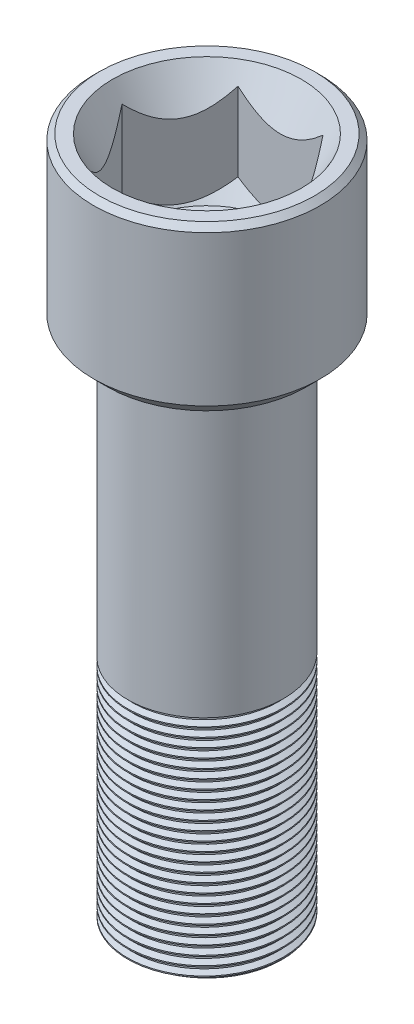
SolidWorks part; units mm, degrees
ref_plane "Front Plane" through (0, 0, 0) normal (0, 0, 1) x (1, 0, 0)
ref_plane "Top Plane" through (0, 0, 0) normal (0, 1, 0) x (1, 0, 0)
ref_plane "Right Plane" through (0, 0, 0) normal (1, 0, 0) x (0, 0, -1)
sketch "Sketch1" plane through (0, 0, 0) normal (0, 1, 0) x (1, 0, 0)
  circle A0 centre (0, 0) radius 4
  dimension "D1" = 8
extrude "Boss-Extrude1" add sketch "Sketch1" against normal blind 12
sketch "Sketch2" plane through (0, -12, 0) normal (0, -1, 0) x (1, 0, 0)
  circle A0 centre (0, 0) radius 2.75
  dimension "D1" = 5.5
extrude "Boss-Extrude2" add sketch "Sketch2" along normal blind 20
sketch "Sketch3" plane through (0, 0, 0) normal (0, 1, 0) x (1, 0, 0)
  line L1 (4.5, 0) -> (2.25, 3.8971)
  line L2 (2.25, 3.8971) -> (-2.25, 3.8971)
  line L3 (-2.25, 3.8971) -> (-4.5, 0)
  line L4 (-4.5, 0) -> (-2.25, -3.8971)
  line L5 (-2.25, -3.8971) -> (2.25, -3.8971)
  line L6 (2.25, -3.8971) -> (4.5, 0)
  circle A0 centre (0, 0) radius 3.8971 construction
  dimension "D1" = 4.5
extrude "Cut-Extrude1" cut sketch "Sketch3" against normal blind 6
chamfer "Chamfer2" distance 0.5 angle 45 1 edges at (0, -12, 4)
thread "Thread2" pitch 0.3175 method cut profile "Thread Profile6" start angle 0, offset 0, length 0, pitch 0.3175, diameter 5.5
ref_plane "Plane7" through (2.75, -32, 0) normal (0, 0, 1) x (1, 0, 0)
sketch "Thread Profile6" plane through (2.75, -32, 0) normal (0, 0, 1) x (1, 0, 0)
  line L0 (0, 0) -> (0, 0.3175) construction
  line L11 (0, 0) -> (0, 0.2778)
  line L12 (0, 0.2778) -> (-0.1719, 0.1786)
  line L13 (-0.1719, 0.1786) -> (-0.1719, 0.0992)
  line L15 (-0.1719, 0.0992) -> (0, 0)
  line L17 (-0.1719, 0.1389) -> (0, 0.1389) construction
  point P2 (0, 0)
  dimension "Pitch" = 0.3175
  dimension "Profile_Angle" = 60
  dimension "Profile_Land" = 0.0794
  dimension "Profile_Height" = 0.1719
sketch "Sketch59" plane through (0, -32, 0) normal (0, -1, 0) x (1, 0, 0)
  circle A0 centre (0, 0) radius 7.5
  dimension "D1" = 15
extrude "Cut-Extrude2" cut sketch "Sketch59" against normal blind 2
sketch "Sketch60" plane through (0, 0, 0) normal (0, 1, 0) x (1, 0, 0)
  circle A0 centre (0, 0) radius 7.5
  dimension "D1" = 15
extrude "Cut-Extrude3" cut sketch "Sketch60" against normal blind 3
sketch "Sketch61" plane through (0, -6, 0) normal (0, 1, 0) x (1, 0, 0)
  circle A0 centre (0, 0) radius 4.8158
extrude "Cut-Extrude4" cut sketch "Sketch61" along normal blind 10
sketch "Sketch62" plane through (0, -6, 0) normal (0, 1, 0) x (1, 0, 0)
  line L1 (3, 0) -> (1.5, 2.5981)
  line L2 (1.5, 2.5981) -> (-1.5, 2.5981)
  line L3 (-1.5, 2.5981) -> (-3, 0)
  line L4 (-3, 0) -> (-1.5, -2.5981)
  line L5 (-1.5, -2.5981) -> (1.5, -2.5981)
  line L6 (1.5, -2.5981) -> (3, 0)
  circle A0 centre (0, 0) radius 2.5981 construction
  dimension "D1" = 3
extrude "Cut-Extrude5" cut sketch "Sketch62" against normal blind 4
sketch "Sketch64" plane through (0, 0, 0) normal (0, 0, 1) x (1, 0, 0)
  line L0 (-2.4061, -6) -> (-3, -6.9824)
  line L1 (4, -6) -> (-4, -6) construction
  line L2 (-3, -10) -> (-3, -6) construction
  line L3 (-3, -6.9824) -> (-3, -6)
  line L4 (-3, -6) -> (-2.4061, -6)
sketch "Sketch65" plane through (0, 0, 0) normal (0, 0, 1) x (1, 0, 0)
  line L0 (-3, -6) -> (-2.1943, -6)
  line L1 (4, -6) -> (-4, -6) construction
  line L2 (-2.1943, -6) -> (-3, -7.3047)
  line L3 (-3, -10) -> (-3, -6) construction
  line L4 (-3, -7.3047) -> (-3, -6)
chamfer "Chamfer4" distance 0.2 1 edges at (-2.25, -6, -1.299)
chamfer "Chamfer5" distance 0.2 angle 45 1 edges at (-2.3077, -6, 1.199)
chamfer "Chamfer6" distance 0.2 angle 45 1 edges at (-0.1155, -6, -2.5981)
chamfer "Chamfer7" distance 0.2 angle 45 1 edges at (2.1923, -6, -1.399)
chamfer "Chamfer8" distance 0.2 angle 45 2 edges at (-0.1155, -6, 2.5981) (2.3077, -6, 1.199)
chamfer "Chamfer9" distance 0.2 angle 45 1 edges at (0, -6, 4)
sketch "Sketch69" plane through (0, 0, 0) normal (0, 0, 1) x (1, 0, 0)
  line L0 (0, 0) -> (0, -50000) construction
  line L1 (-3, -9.3662) -> (-2.5455, -10)
  line L2 (-3, -10) -> (-3, -6.2) construction
  line L3 (-3, -10) -> (-1.5, -10) construction
  line L4 (-2.5455, -10) -> (-3, -10)
  line L5 (-3, -10) -> (-3, -9.3662)
revolve "Revolve1" add sketch "Sketch69" angle 360 about L0
sketch "Sketch70" plane through (0, 0, 0) normal (0, 0, 1) x (1, 0, 0)
  line L6 (0, 0) -> (0, -50000) construction
  line L8 (-3.5176, -5.7194) -> (-1.0203, -8.057)
  line L9 (-1.0203, -8.057) -> (-1.0203, -5.7194)
  line L10 (-1.0203, -5.7194) -> (-3.5176, -5.7194)
sketch "Sketch71" plane through (0, 0, 0) normal (0, 0, 1) x (1, 0, 0)
  line L0 (0, 0) -> (0, -50000) construction
  line L1 (-3.5281, -5.6564) -> (-1.9269, -8.4971)
  line L2 (-1.9269, -8.4971) -> (-1.9269, -5.6564)
  line L3 (-1.9269, -5.6564) -> (-3.5281, -5.6564)
revolve "Cut-Revolve17" cut sketch "Sketch71" angle 360 about L0
